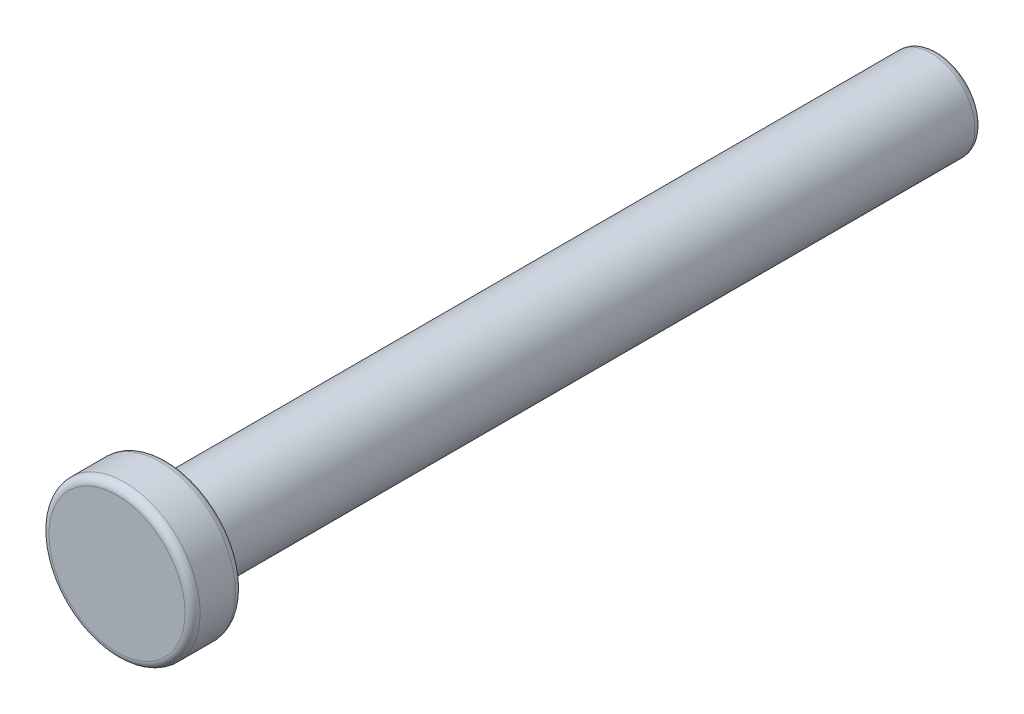
SolidWorks part; units mm, degrees
ref_plane "前视基准面" through (0, 0, 0) normal (0, 0, 1) x (1, 0, 0)
ref_plane "上视基准面" through (0, 0, 0) normal (0, 1, 0) x (1, 0, 0)
ref_plane "右视基准面" through (0, 0, 0) normal (1, 0, 0) x (0, 0, -1)
other "Configuration Table"
sketch "草图1" plane through (0, 0, 0) normal (0, 0, 1) x (1, 0, 0)
  circle A0 centre (0, 0) radius 1.75
  circle A1 centre (0, 0) radius 3
  dimension "D1" = 3.5
  dimension "D2" = 6
extrude "凸台-拉伸1" add sketch "草图1" along normal blind 2 contours A0 | A1 A0 region at (0, 0, 0) region at (-2.9151, 0, 0)
extrude "凸台-拉伸2" add sketch "草图1<3>" against normal blind 30.6 contours A0 region at (0, 0, 0)
sketch "草图1<3>" plane through (0, 0, 0) normal (0, 0, 1) x (1, 0, 0) same geometry as "草图1"
fillet "圆角1" radius 0.3 4 edges at (3, 0, 0) (1.75, 0, 0) (3, 0, 2) (1.75, 0, -30.6)
